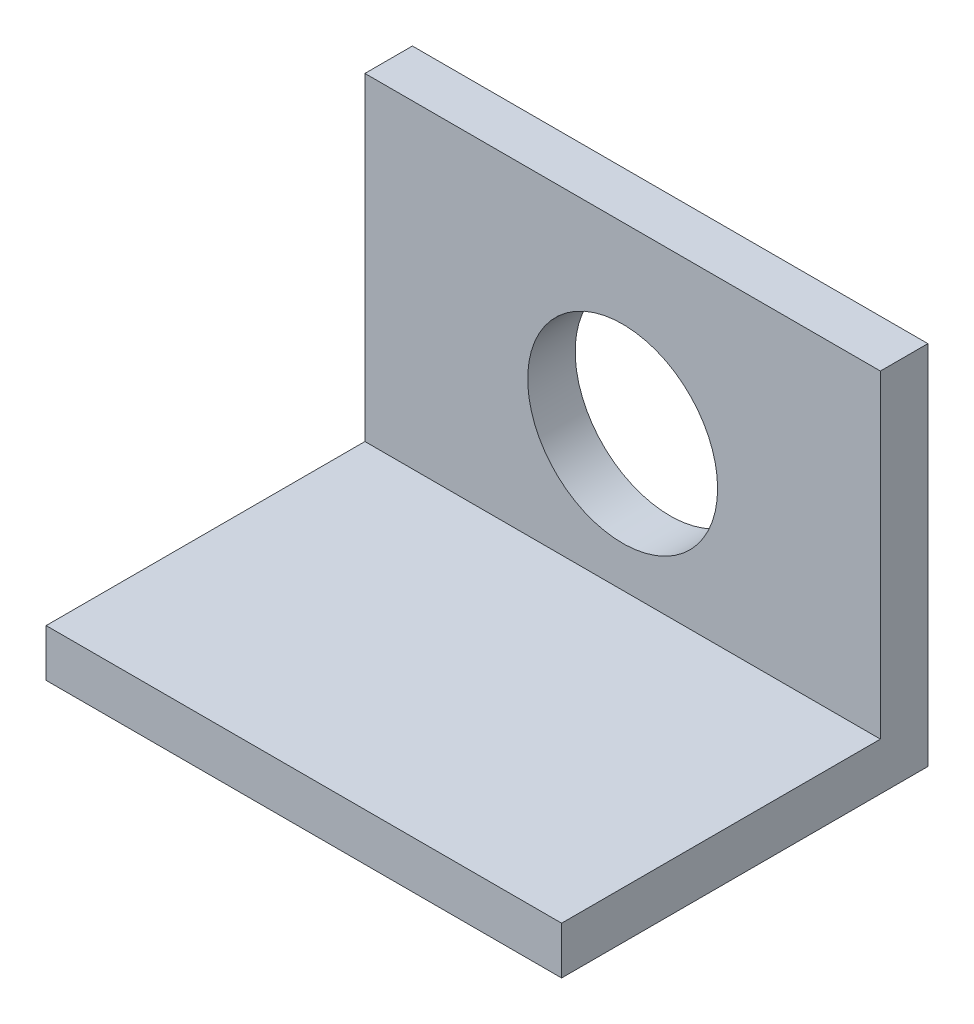
SolidWorks part; units mm, degrees
ref_plane "Plan de face" through (0, 0, 0) normal (0, 0, 1) x (1, 0, 0)
ref_plane "Plan de dessus" through (0, 0, 0) normal (0, 1, 0) x (1, 0, 0)
ref_plane "Plan de droite" through (0, 0, 0) normal (1, 0, 0) x (0, 0, -1)
sketch "Esquisse1" plane through (0, 0, 0) normal (0, 0, 1) x (1, 0, 0)
  line L0 (-19, 3.5) -> (19, 3.5)
  line L1 (-19, 27) -> (19, 27)
  line L2 (-19, 27) -> (-19, 0)
  line L3 (-19, 0) -> (19, 0)
  line L4 (19, 27) -> (19, 0)
  line L5 (-19, 27) -> (19, 0) construction
  line L6 (-19, 0) -> (19, 27) construction
  circle A0 centre (0, 13.5) radius 7
  point P0 (0, 13.5)
  dimension "D4" = 14
  dimension "D1" = 38
  dimension "D2" = 27
  dimension "D3" = 3.5
extrude "Boss.-Extru.1" add sketch "Esquisse1" along normal blind 3.5 contours L4 L1 L2 L0 A0 region at (-18.5532, 15.25, 0)
extrude "Boss.-Extru.2" add sketch "Esquisse1<4>" along normal blind 27 contours L4 L0 L2 L3 region at (0, 1.75, 0)
sketch "Esquisse1<4>" plane through (0, 0, 0) normal (0, 0, 1) x (1, 0, 0) same geometry as "Esquisse1"
sketch "Esquisse2" plane through (0, 3.5, 0) normal (0, 1, 0) x (1, 0, 0)
  line L0 (-18.1866, -15.7565) -> (9.8134, -15.7565)
  line L2 (-18.1866, -15.7565) -> (-10.1866, -15.7565)
  line L3 (9.8134, -15.7565) -> (1.8134, -15.7565)
  line L4 (-19, -27) -> (19, -27) construction
  dimension "D1" = 28
  dimension "D2" = 8
  dimension "D3" = 8
  dimension "D4" = 11.2435
